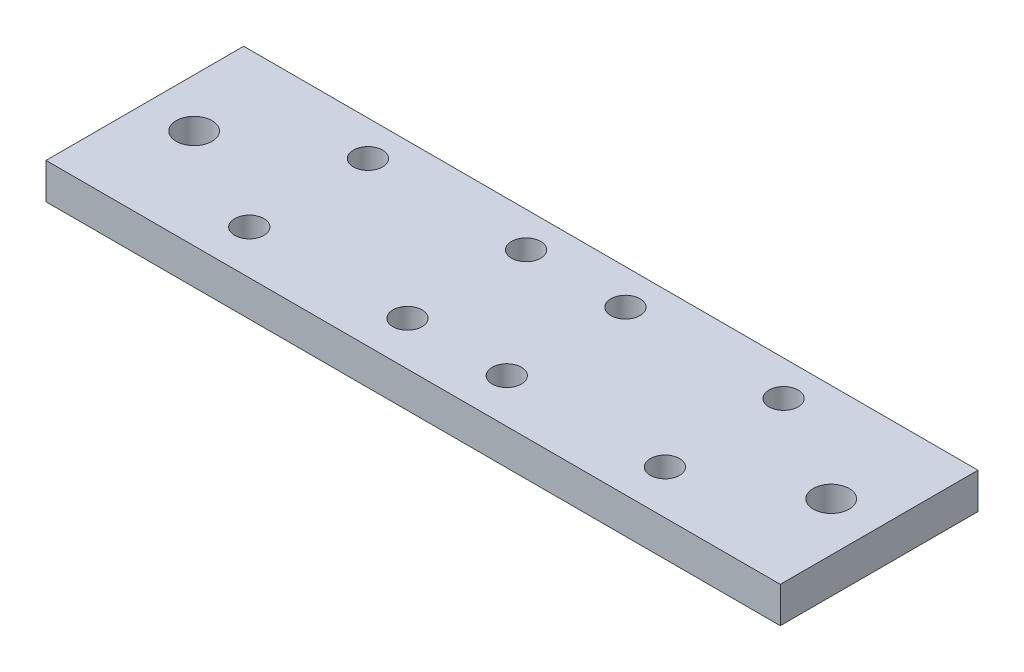
SolidWorks part; units mm, degrees
material "Alumina"
ref_plane "Front Plane" through (0, 0, 0) normal (0, 0, 1) x (1, 0, 0)
ref_plane "Top Plane" through (0, 0, 0) normal (0, 1, 0) x (1, 0, 0)
ref_plane "Right Plane" through (0, 0, 0) normal (1, 0, 0) x (0, 0, -1)
sketch "Sketch1" plane through (0, 0, 0) normal (0, 1, 0) x (1, 0, 0)
  line L1 (0, 0) -> (130, 0)
  line L2 (0, 0) -> (0, -35)
  line L3 (0, -35) -> (130, -35)
  line L4 (130, 0) -> (130, -35)
  dimension "D1" = 130
  dimension "D2" = 35
extrude "Boss-Extrude1" add sketch "Sketch1" along normal blind 6.35
sketch "Sketch5" plane through (0, 6.35, 0) normal (0, 1, 0) x (1, 0, 0)
  line L1 (0, 0) -> (0, -35) construction
  line L2 (130, -35) -> (130, 0) construction
  circle A0 centre (8.605, -17.3826) radius 3.18
  circle A2 centre (121.395, -17.3826) radius 3.18
  dimension "D1" = 8.605
  dimension "D2" = 8.605
extrude "Cut-Extrude2" cut sketch "Sketch5" against normal through all
sketch "Sketch8" plane through (0, 0, 0) normal (0, -1, 0) x (1, 0, 0)
  circle A16 centre (28.2101, 6.2138) radius 2.5866 construction
  circle A17 centre (28.2101, 27.2138) radius 2.5866 construction
  circle A18 centre (56.2101, 27.2138) radius 2.5866 construction
  circle A19 centre (56.2101, 6.2138) radius 2.5866 construction
  circle A20 centre (73.7921, 6.2138) radius 2.5866 construction
  circle A21 centre (73.7921, 27.2138) radius 2.5866 construction
  circle A22 centre (101.7921, 6.2138) radius 2.5866 construction
  circle A23 centre (101.7921, 27.2138) radius 2.5866 construction
  circle A24 centre (28.2101, 6.2138) radius 2.5866
  circle A25 centre (28.2101, 27.2138) radius 2.5866
  circle A26 centre (56.2101, 27.2138) radius 2.5866
  circle A27 centre (56.2101, 6.2138) radius 2.5866
  circle A28 centre (73.7921, 6.2138) radius 2.5866
  circle A29 centre (73.7921, 27.2138) radius 2.5866
  circle A30 centre (101.7921, 6.2138) radius 2.5866
  circle A31 centre (101.7921, 27.2138) radius 2.5866
extrude "Cut-Extrude4" cut sketch "Sketch8" against normal through all
